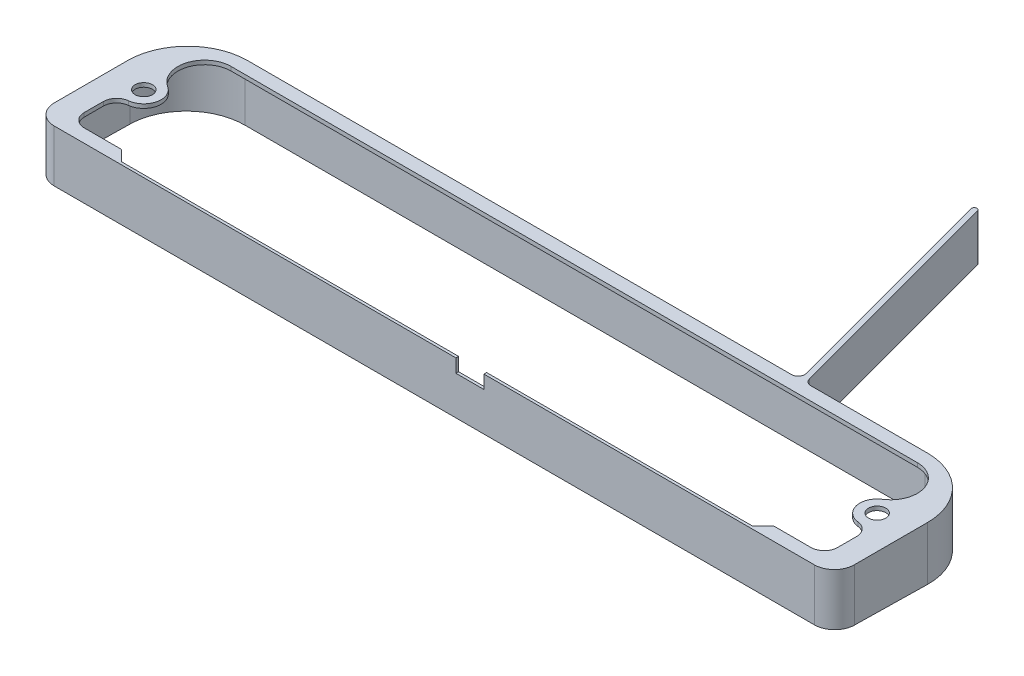
SolidWorks part; units mm, degrees
material "ABS"
ref_plane "Front" through (0, 0, 0) normal (0, 0, 1) x (1, 0, 0)
ref_plane "Top" through (0, 0, 0) normal (0, 1, 0) x (1, 0, 0)
ref_plane "Right" through (0, 0, 0) normal (1, 0, 0) x (0, 0, -1)
ref_axis "X" through (-80.9, 0, 0) along (1, 0, 0)
ref_axis "Y" through (0, -50, 0) along (0, 1, 0)
ref_axis "Z" through (0, 0, -80.9) along (0, 0, 1)
sketch "Sketch1" plane through (0, 0, 0) normal (0, 1, 0) x (1, 0, 0)
  line L0 (-57, 0) -> (-56.5, 0)
  line L2 (-51.4595, 21) -> (51.4595, 21)
  line L4 (56.5, 0) -> (57, 0)
  line L5 (60, 3) -> (60, 14)
  line L6 (51, 23) -> (-51, 23)
  line L7 (-60, 14) -> (-60, 3)
  line L8 (-56.5, 0) -> (56.5, 0)
  line L9 (-49, 0.4) -> (49, 0.4)
  line L10 (-56.5, 0) -> (-56.5, 0.4) construction
  line L11 (56.5, 0) -> (56.5, 0.4) construction
  line L12 (55, 11.43) -> (-55, 11.43) construction
  line L13 (0, 11.43) -> (0, 0) construction
  line L14 (56.5, 2) -> (49, 2)
  line L15 (49, 2) -> (49, 0.4)
  line L16 (-56.5, 2) -> (-49, 2)
  line L17 (-49, 2) -> (-49, 0.4)
  line L18 (-56.5, 0.4) -> (-56.5, 2) construction
  line L19 (-56.5, 0.4) -> (-49, 0.4) construction
  line L20 (56.5, 2) -> (56.5, 0.4) construction
  line L21 (49, 0.4) -> (56.5, 0.4) construction
  line L22 (56.5, 6.8573) -> (56.5, 2)
  line L23 (-56.5, 2) -> (-56.5, 6.8573)
  arc A0 (-53.6053, 13.6242) -> (-51.4595, 21) centre (-51.4595, 17) cw
  arc A1 (51.4595, 21) -> (53.6053, 13.6242) centre (51.4595, 17) cw
  arc A2 (60, 14) -> (51, 23) centre (51, 14) ccw
  arc A3 (-51, 23) -> (-60, 14) centre (-51, 14) ccw
  circle A4 centre (55, 11.43) radius 1.3
  circle A5 centre (-55, 11.43) radius 1.3
  arc A6 (53.6053, 13.6242) -> (54.7174, 8.8454) centre (55, 11.43) ccw
  arc A7 (-53.6053, 13.6242) -> (-54.7174, 8.8454) centre (-55, 11.43) cw
  arc A8 (-54.7174, 8.8454) -> (-56.5, 6.8573) centre (-54.5, 6.8573) ccw
  arc A9 (56.5, 6.8573) -> (54.7174, 8.8454) centre (54.5, 6.8573) ccw
  arc A10 (-57, 0) -> (-60, 3) centre (-57, 3) cw
  arc A11 (60, 3) -> (57, 0) centre (57, 3) cw
  dimension "D5" = 9
  dimension "D6" = 4
  dimension "D10" = 2.6
  dimension "D13" = 2.6
  dimension "D14" = 2
  dimension "D15" = 3
  dimension "D1" = 120
  dimension "D2" = 3.5
  dimension "D3" = 2
  dimension "D4" = 23
  dimension "D7" = 0.4
  dimension "D8" = 11.43
  dimension "D9" = 110
  dimension "D11" = 11
  dimension "D12" = 2
extrude "Boss-Extrude1" add sketch "Sketch1" along normal blind 0.6
sketch "Sketch8" plane through (0, 0, 0) normal (0, -1, 0) x (-1, 0, 0)
  line L4 (51, 22.6) -> (-51, 22.6)
  line L5 (-59.6, 14) -> (-59.6, 3)
  line L12 (-57, 0.4) -> (57, 0.4)
  line L13 (59.6, 3) -> (59.6, 14)
  line L14 (-57, 0) -> (57, 0)
  line L15 (60, 3) -> (60, 14)
  line L16 (51, 23) -> (-51, 23)
  line L17 (-60, 14) -> (-60, 3)
  line L18 (-57, 0) -> (57, 0)
  line L19 (60, 3) -> (60, 14)
  line L20 (51, 23) -> (-51, 23)
  line L21 (-60, 14) -> (-60, 3)
  arc A6 (-51, 22.6) -> (-59.6, 14) centre (-51, 14) ccw
  arc A7 (-59.6, 3) -> (-57, 0.4) centre (-57, 3) ccw
  arc A8 (57, 0.4) -> (59.6, 3) centre (57, 3) ccw
  arc A9 (59.6, 14) -> (51, 22.6) centre (51, 14) ccw
  arc A14 (-60, 3) -> (-57, 0) centre (-57, 3) ccw
  arc A15 (57, 0) -> (60, 3) centre (57, 3) ccw
  arc A16 (60, 14) -> (51, 23) centre (51, 14) ccw
  arc A17 (-51, 23) -> (-60, 14) centre (-51, 14) ccw
  arc A18 (-60, 3) -> (-57, 0) centre (-57, 3) ccw
  arc A19 (57, 0) -> (60, 3) centre (57, 3) ccw
  arc A20 (60, 14) -> (51, 23) centre (51, 14) ccw
  arc A21 (-51, 23) -> (-60, 14) centre (-51, 14) ccw
  dimension "D1" = 0
  dimension "D2" = 0.4
extrude "Boss-Extrude2" add sketch "Sketch8" along normal blind 8.2 from surface starting at face at (0, 0.6, -10.3107)
chamfer "Chamfer1" distance 0.6 angle 45 9 edges at (53, 0, -0.4) (-53, 0, -0.4) (58.8385, 0, -1.1615) (-58.8385, 0, -1.1615) (59.6, 0, -8.5) (-59.6, 0, -8.5) (57.0811, 0, -20.0811) (-57.0811, 0, -20.0811) (0, 0, -22.6)
sketch "Sketch9" plane through (0, 0, 0) normal (1, 0, 0) x (0, 0, -1)
  line L0 (-2, -7.6) -> (23, -7.6)
  line L1 (23, -7.6) -> (-2, -7.1636)
  line L3 (-2, -7.1636) -> (-2, -7.6)
  dimension "D1" = 25
  dimension "D2" = 1
extrude "Cut-Extrude1" cut sketch "Sketch9" against normal through all both and the other way through all
sketch "Sketch11" plane through (0, 0, 0) normal (0, 0, 1) x (1, 0, 0)
  line L0 (3.25, 0.6) -> (3.25, -1.4)
  line L1 (-57, 0.6) -> (57, 0.6) construction
  line L2 (3.25, -1.4) -> (7.45, -1.4)
  line L3 (7.45, -1.4) -> (7.45, 0.6)
  line L4 (7.45, 0.6) -> (3.25, 0.6)
  line L5 (5.35, -1.4) -> (5.35, 0.6) construction
  line L7 (60, 0.6) -> (60, -7.1985) construction
  dimension "D1" = 54.65
  dimension "D2" = 4.2
  dimension "D3" = 2
extrude "Cut-Extrude2" cut sketch "Sketch11" against normal up to next
fillet "Fillet1" radius 2 2 edges at (-56.5, 0.3, -2) (56.5, 0.3, -2)
chamfer "Chamfer2" distance 1.7 angle 45 2 edges at (-49, 0, -0.4) (49, 0, -0.4)
sketch "Sketch12" plane through (0, 0, 0) normal (0, 1, 0) x (1, 0, 0)
  line L1 (-57, 0) -> (57, 0) construction
  line L3 (-70.0161, 72.0463) -> (123.9526, 72.0463) construction
  line L10 (7.45, 0) -> (57, 0) construction
  line L11 (0, 38.0905) -> (0, 0) construction
  line L14 (23.2727, 58.2071) -> (32.7064, 23)
  line L30 (31.8782, 23) -> (22.5, 58)
  line L39 (31.8782, 23) -> (32.7064, 23)
  line L40 (51, 23) -> (-51, 23) construction
  arc A6 (22.5, 58) -> (23.2727, 58.2071) centre (22.8864, 58.1035) cw
  dimension "D3" = 72.0463
  dimension "D1" = 22.5
  dimension "D2" = 35
  dimension "D4" = 15
  dimension "D5" = 0.8
extrude "Boss-Extrude3" add sketch "Sketch12" against normal blind 7 from surface starting at face at (0.7643, 0.6, -7.1934)
fillet "Fillet2" radius 1 2 edges at (31.8782, -2.9, -23) (32.7064, -2.9, -23)
equation "\"D3@Sketch12\"=200-127.95373"
